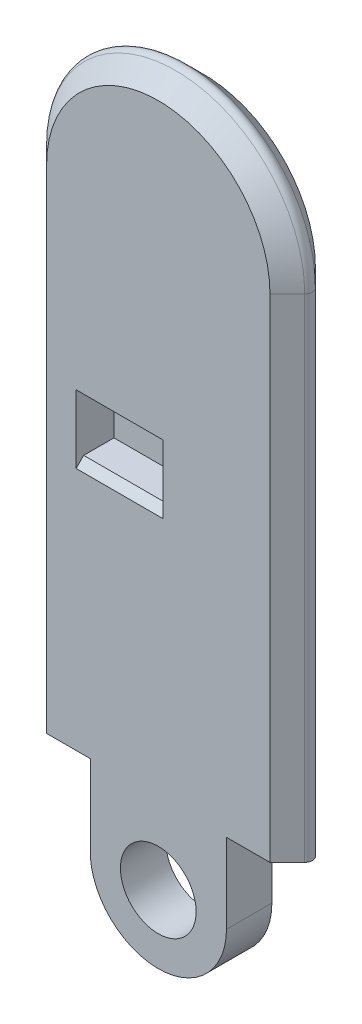
SolidWorks part; units mm, degrees
ref_plane "Płaszczyzna przednia" through (0, 0, 0) normal (0, 0, 1) x (1, 0, 0)
ref_plane "Płaszczyzna górna" through (0, 0, 0) normal (0, 1, 0) x (1, 0, 0)
ref_plane "Płaszczyzna prawa" through (0, 0, 0) normal (1, 0, 0) x (0, 0, -1)
sketch "Szkic1" plane through (0, 0, 0) normal (0, 0, 1) x (1, 0, 0)
  line L1 (-17.75, 32.5) -> (17.75, 32.5)
  line L2 (-17.75, 32.5) -> (-17.75, -32.5)
  line L3 (-17.75, -32.5) -> (17.75, -32.5)
  line L4 (17.75, 32.5) -> (17.75, -32.5)
  line L5 (-17.75, 32.5) -> (17.75, -32.5) construction
  line L6 (-17.75, -32.5) -> (17.75, 32.5) construction
  circle A0 centre (0, 32.5) radius 17.75
  point P0 (0, 0)
  dimension "D1" = 35.5
  dimension "D2" = 65
extrude "Dodanie-wyciągnięcie1" add sketch "Szkic1" against normal blind 6 contours L1 A0 | L1 A0 | A0 L2 L3 L4 region at (0, 40.0333, 0) region at (0, -6.8167, 0) region at (0, 24.9667, 0)
chamfer "Sfazowanie1" distance 3 angle 45 6 edges at (17.75, 0, -6) (0, 50.25, -6) (-17.75, 0, -6) (17.75, 0, 0) (0, 50.25, 0) (-17.75, 0, 0)
fillet "Zaokrąglenie1" radius 1 3 edges at (17.75, 0, -3) (0, 50.25, -3) (-17.75, 0, -3)
sketch "Szkic2" plane through (0, 0, 0) normal (0, 0, 1) x (1, 0, 0)
  line L0 (-5.1, 1.25) -> (-5.1, 8.6301) construction
  line L2 (0.65, 8.75) -> (-10.85, 8.75)
  line L3 (0.65, 8.75) -> (0.65, 0.75)
  line L4 (-10.35, 1.25) -> (-10.35, 7.75) construction
  line L5 (-10.35, 7.75) -> (0.15, 7.75) construction
  line L6 (0.15, 1.25) -> (0.15, 7.75) construction
  line L7 (-10.35, 1.25) -> (0.15, 1.25) construction
  line L8 (0.65, 0.75) -> (-10.85, 0.75)
  line L9 (-10.85, 8.75) -> (-10.85, 0.75)
  line L10 (0.65, 8.75) -> (-10.85, 0.75) construction
  line L11 (0.65, 0.75) -> (-10.85, 8.75) construction
  point P6 (-5.1, 4.75)
  point P11 (-11.2215, 9.4657)
  dimension "D1" = 1
  dimension "D2" = 0.5
  dimension "D3" = 8
extrude "Wytnij-wyciągnięcie1" cut sketch "Szkic2" against normal blind 5
sketch "Szkic3" plane through (0, 0, -6) normal (0, 0, -1) x (-1, 0, 0)
  line L1 (0, -24) -> (8, -24) construction
  line L2 (4, -24) -> (4, -27.15) construction
  line L4 (-0.5, -30.4) -> (8.5, -30.4)
  line L5 (-0.5, -30.4) -> (-0.5, -23.9)
  line L6 (-0.5, -23.9) -> (8.5, -23.9)
  line L7 (8.5, -30.4) -> (8.5, -23.9)
  line L8 (-0.5, -30.4) -> (8.5, -23.9) construction
  line L9 (-0.5, -23.9) -> (8.5, -30.4) construction
  point P8 (0, -30)
  point P9 (8, -29.7935)
  point P10 (-0.8737, -30)
  point P11 (9.0203, -23.8)
  point P12 (4, -24)
  point P13 (0, 0)
  point P14 (4, -24)
  dimension "D1" = 0.1
  dimension "D2" = 9
  dimension "D3" = 6.5
extrude "Wytnij-wyciągnięcie2" cut sketch "Szkic3" against normal blind 4.5
chamfer "Sfazowanie2" distance 0.5 angle 45 1 edges at (-4, -23.9, -6)
chamfer "Sfazowanie3" distance 1 angle 45 1 edges at (-5.1, 0.75, 0)
sketch "Szkic4" plane through (0, 0, 0) normal (0, 0, 1) x (1, 0, 0)
  line L0 (0, -32.5) -> (0, -43.0308) construction
  line L1 (-14.75, -32.5) -> (14.75, -32.5) construction
  line L2 (9, -43.0308) -> (9, -32.5)
  line L3 (9, -32.5) -> (-8.9747, -32.5)
  line L4 (-8.9747, -32.5) -> (-8.9747, -43.7054)
  circle A0 centre (0, -43.0308) radius 5
  circle A1 centre (0, -43.0308) radius 9
  point P9 (0, -43.0308)
  line M6 (-14.75, -32.5) -> (14.75, -32.5)
  dimension "D1" = 4
  dimension "D2" = 10
extrude "Dodanie-wyciągnięcie2" add sketch "Szkic4" against normal blind 6 contours L3 L0 A1 L2 | A1 A0 L4 | L0 L4 A1 M6 region at (5.8889, -34.8139, 0) region at (-5.8633, -34.7913, 0) region at (6.1841, -36.8467, 0)
